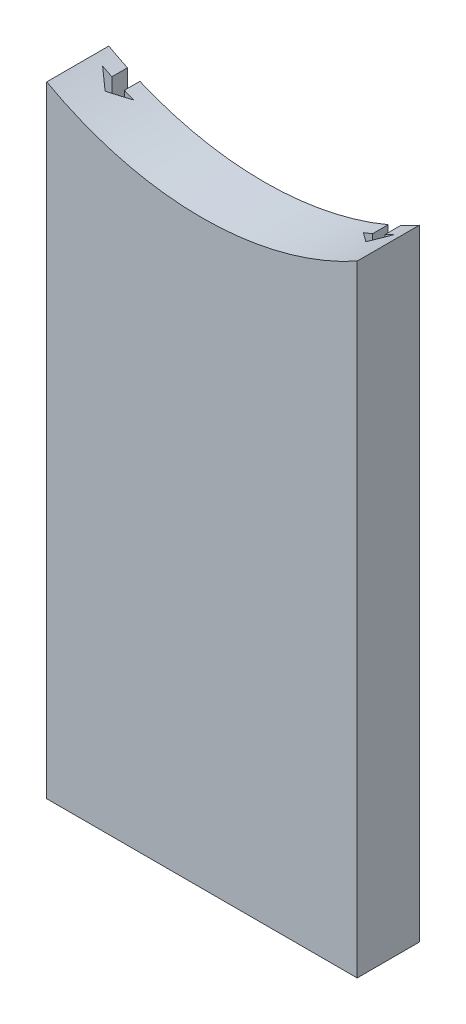
SolidWorks part; units mm, degrees
ref_plane "Alzado" through (0, 0, 0) normal (0, 0, 1) x (1, 0, 0)
ref_plane "Planta" through (0, 0, 0) normal (0, 1, 0) x (1, 0, 0)
ref_plane "Vista lateral" through (0, 0, 0) normal (1, 0, 0) x (0, 0, -1)
sketch "Croquis1" plane through (0, 0, 0) normal (0, 1, 0) x (1, 0, 0)
  line L0 (-25, 0) -> (25, 0)
  line L1 (-25, 0) -> (-25, 10)
  line L2 (-25, 10) -> (-22, 10)
  line L3 (-17, 10) -> (-17, 3.9635)
  line L4 (-17, 3.9635) -> (17, 3.9635)
  line L5 (17, 3.9635) -> (17, 10)
  line L6 (17, 10) -> (20, 10)
  line L7 (25, 10) -> (25, 0)
  line L8 (0, -1.1135) -> (0, 19.1205) construction
  line L9 (-23.5, 7.5) -> (-22, 7.5)
  line L11 (-20, 10) -> (-20, 7.5)
  line L13 (-22, 10) -> (-22, 7.5)
  line L14 (22, 10) -> (25, 10)
  line L16 (-20, 7.5) -> (-18.5, 7.5)
  line L17 (-23.5, 7.5) -> (-21, 5.4004)
  line L18 (-21, 5.4004) -> (-18.5, 7.5)
  line L19 (23.5, 7.5) -> (22, 7.5)
  line L20 (23.5, 7.5) -> (21, 5.4004)
  line L21 (21, 5.4004) -> (18.5, 7.5)
  line L22 (20, 7.5) -> (18.5, 7.5)
  line L23 (20, 10) -> (20, 7.5)
  line L25 (22, 10) -> (22, 7.5)
  line L26 (-20, 10) -> (-17, 10)
  point P11 (-21, 12.065)
  dimension "D1" = 50
  dimension "D2" = 8
  dimension "D3" = 8
  dimension "D4" = 10
  dimension "D5" = 5
  dimension "D6" = 1.5
  dimension "D7" = 2.5
  dimension "D8" = 2
  dimension "D9" = 10
extrude "Saliente-Extruir1" add sketch "Croquis1" along normal blind 100
sketch "Croquis4" plane through (0, 0, -3.9635) normal (0, 0, -1) x (-1, 0, 0)
  line L0 (19.3731, 58.0222) -> (36.4852, 58.0222)
  line L8 (36.4852, 78.0249) -> (36.4852, 58.0222)
  line L11 (19.3731, 78.0249) -> (36.4852, 78.0249)
  arc A1 (19.3731, 78.0249) -> (19.3731, 58.0222) centre (0, 68.0235) ccw
  point P5 (0, 0)
  dimension "D3" = 20.0027
sketch "Croquis6" plane through (0, 0, -3.9635) normal (0, 0, -1) x (-1, 0, 0)
  line L0 (17, 100) -> (17, 0) construction
  line L1 (17, 0) -> (-17, 0)
  line L2 (17, 0) -> (17, 54.3728)
  line L4 (-17, 0) -> (-17, 54.3728)
  arc A0 (17, 54.3728) -> (-17, 54.3728) centre (0, 68.3256) cw
  arc A1 (19.3731, 78.0249) -> (19.3731, 58.0222) centre (0, 68.0235) ccw construction
  point P5 (17, 54.3728)
  point P9 (-16.8216, 54.1373)
  point P10 (-17, 54.3728)
extrude "Saliente-Extruir2" add sketch "Croquis6" along normal up to surface (6.0365 mm away) up to face at (-18.5, 50, -10)
sketch "Croquis7" plane through (0, 0, -10) normal (0, 0, -1) x (-1, 0, 0)
  arc A0 (-25, 100) -> (25, 100) centre (0, 145.1593) ccw
  arc A1 (-25, 100) -> (25, 100) centre (0, 80.1817) cw
extrude "Cortar-Extruir4" cut sketch "Croquis7" against normal blind 10
sketch "Croquis9" plane through (0, 0, -3.9635) normal (0, 0, -1) x (-1, 0, 0)
  line L5 (17, 54.3728) -> (17, 96.4216)
  line L6 (-17, 96.4216) -> (-17, 54.3728)
  line L10 (17, 82.2784) -> (17, 96.4216)
  line L11 (-17, 96.4216) -> (-17, 82.2784)
  arc A0 (17, 82.2784) -> (-17, 82.2784) centre (0, 68.3256) ccw
  arc A5 (-17, 96.4216) -> (17, 96.4216) centre (0, 145.1593) ccw
  arc A7 (-17, 54.3728) -> (17, 54.3728) centre (0, 68.3256) ccw
  arc A10 (-17, 96.4216) -> (17, 96.4216) centre (0, 145.1593) ccw
  dimension "D1" = 0
extrude "Cortar-Extruir5" cut sketch "Croquis4" along normal blind 10
extrude "Saliente-Extruir3" add sketch "Croquis9" along normal up to surface (6.0365 mm away) up to face at (18.5438, 88.1126, -10)
